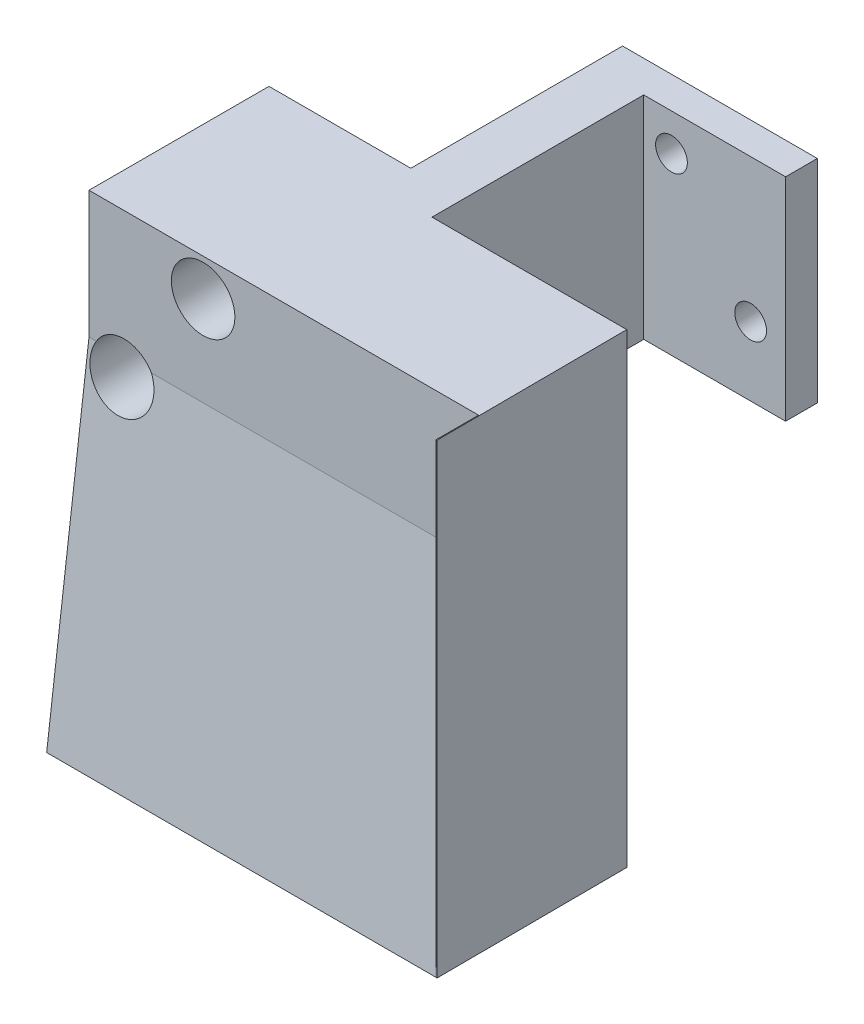
SolidWorks part; units mm, degrees
ref_plane "Front Plane" through (0, 0, 0) normal (0, 0, 1) x (1, 0, 0)
ref_plane "Top Plane" through (0, 0, 0) normal (0, 1, 0) x (1, 0, 0)
ref_plane "Right Plane" through (0, 0, 0) normal (1, 0, 0) x (0, 0, -1)
sketch "Sketch1" plane through (0, 0, 0) normal (0, 1, 0) x (1, 0, 0)
  line L0 (0, 0) -> (18.4, 0)
  line L1 (18.4, 0) -> (18.4, 20)
  line L2 (18.4, 20) -> (31.8, 20)
  line L3 (31.8, 20) -> (31.8, 23)
  line L4 (31.8, 23) -> (13.4, 23)
  line L5 (13.4, 23) -> (13.4, 3)
  line L6 (13.4, 3) -> (0, 3)
  line L7 (0, 3) -> (0, 0)
  dimension "D1" = 13.4
  dimension "D2" = 5
  dimension "D3" = 3
  dimension "D4" = 17
extrude "Boss-Extrude1" add sketch "Sketch1" along normal blind 20
sketch "Sketch2" plane through (0, 0, -20) normal (0, 0, 1) x (1, 0, 0)
  line L1 (31.8, 20) -> (31.8, 0) construction
  line L3 (18.4, 0) -> (31.8, 0) construction
  circle A0 centre (21.02, 16.5) radius 1.5
  circle A1 centre (28.5, 6.5) radius 1.5
  dimension "D1" = 3
  dimension "D2" = 16.5
  dimension "D3" = 10.78
  dimension "D4" = 3.3
  dimension "D5" = 6.5
extrude "Cut-Extrude1" cut sketch "Sketch2" against normal through all both and the other way through all
ref_plane "Plane1" through (15.9, 0, 0) normal (-1, 0, 0) x (0, 0, 1)
mirror "Mirror1" about plane through (15.9, 0, 0) normal (-1, 0, 0) of "Cut-Extrude1"
sketch "Sketch5" plane through (0, 0, 0) normal (-1, 0, 0) x (0, 0, 1)
  line L0 (0, 20) -> (0, -24)
  line L1 (0, -24) -> (18, -24)
  line L2 (18, -24) -> (14, 8)
  line L3 (14, 8) -> (14, 20)
  line L4 (14, 20) -> (0, 20)
  line L5 (-3, 0) -> (0, 0) construction
  line L6 (8, -9) -> (8, -19) construction
  line L7 (10.55, -9) -> (10.55, -19)
  line L8 (5.45, -9) -> (5.45, -19)
  arc A0 (10.55, -9) -> (5.45, -9) centre (8, -9) ccw
  arc A1 (5.45, -19) -> (10.55, -19) centre (8, -19) ccw
  point P11 (8, -14)
  point P16 (0, 0)
  dimension "D1" = 12
  dimension "D2" = 14
  dimension "D3" = 18
  dimension "D4" = 24
  dimension "D5" = 10
  dimension "D6" = 5.1
  dimension "D7" = 5
  dimension "D8" = 8
extrude "Boss-Extrude2" add sketch "Sketch5" against normal offset from surface (36.8 mm away) 5 up to face at (31.8, 10, -21.5) offset beyond the face yes
sketch "Sketch6" plane through (0, -24, 0) normal (0, -1, 0) x (1, 0, 0)
  line L0 (36.8, 0) -> (36.8858, 18)
  line L1 (36.8, 18) -> (0, 18) construction
  line L2 (36.8858, 18) -> (36.8, 18)
  line L3 (36.8, 18) -> (36.8, 0)
  point P5 (36.4167, 18)
  point P8 (37.1783, 18)
  dimension "D1" = 0.273
extrude "Boss-Extrude3" add sketch "Sketch6" against normal up to surface (44 mm away) up to face at (20.08, 20, -6.4)
sketch "Sketch7" plane through (0, 0, 0) normal (-1, 0, 0) x (0, 0, 1)
  line L0 (14, -24) -> (14, -9)
  line L1 (0, -24) -> (18, -24) construction
  line L2 (2, -9) -> (2, -24)
  line L3 (2, -24) -> (14, -24)
  arc A0 (14, -9) -> (2, -9) centre (8, -9) ccw
  arc A1 (10.55, -9) -> (5.45, -9) centre (8, -9) ccw construction
  dimension "D1" = 12
extrude "Cut-Extrude4" cut sketch "Sketch7" against normal offset from surface (31.8095 mm away) 5 up to face at (36.8429, -2, 9)
sketch "Sketch8" plane through (0, 0, 0) normal (0, 0, -1) x (-1, 0, 0)
  circle A0 centre (-3.3, 6.5) radius 3
  circle A1 centre (-10.78, 16.5) radius 3
  dimension "D1" = 6
extrude "Cut-Extrude5" cut sketch "Sketch8" against normal through all
